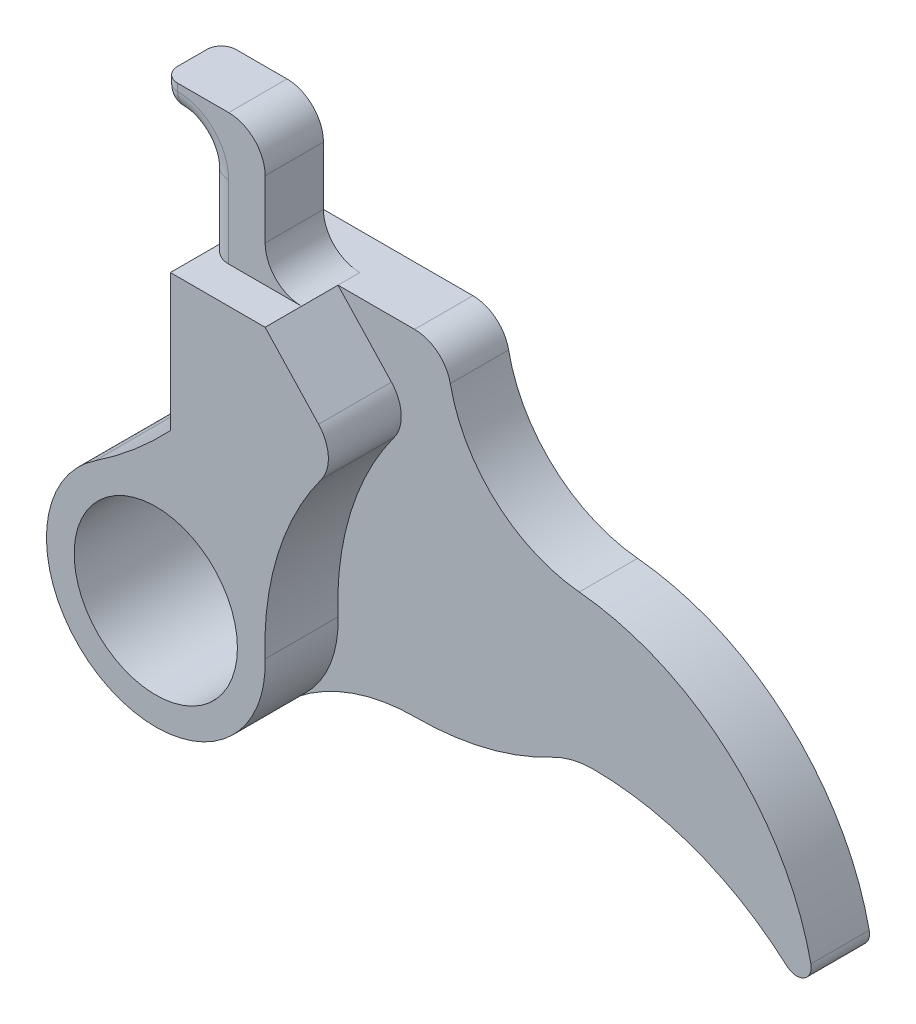
SolidWorks part; units mm, degrees
ref_plane "Спереди" through (0, 0, 0) normal (0, 0, 1) x (1, 0, 0)
ref_plane "Сверху" through (0, 0, 0) normal (0, 1, 0) x (1, 0, 0)
ref_plane "Справа" through (0, 0, 0) normal (1, 0, 0) x (0, 0, -1)
sketch "base" plane through (0, 0, 0) normal (0, 0, 1) x (1, 0, 0)
  line L0 (0, -25) -> (-25, -20) construction
  line L1 (0, 0) -> (9.5671, -23.097) construction
  line L2 (0, 0) -> (-9.5671, -23.097) construction
  line L3 (0, 0) -> (0, -25) construction
  line L4 (0, 0) -> (-2.4504, -24.8796) construction
  line L6 (0, 0) -> (-4.8773, -24.5196) construction
  line L7 (0, -25) -> (25, -20) construction
  line L11 (0, 0) -> (-7.2571, -23.9235) construction
  line L14 (0, 0) -> (7.2571, -23.9235) construction
  line L16 (0, 0) -> (4.8773, -24.5196) construction
  line L18 (0, 0) -> (2.4504, -24.8796) construction
  line L19 (-9.5671, -23.097) -> (9.5671, -23.097) construction
  arc A0 (-7.6537, -18.4776) -> (7.6537, -18.4776) centre (0, 0) ccw construction
  circle A1 centre (0, -25) radius 5 construction
  arc A6 (-9.5671, -23.097) -> (9.5671, -23.097) centre (0, 0) ccw construction
  point P12 (0, -20)
  dimension "D5" = 45
  dimension "D12" = 20
  dimension "ArmA" = 25
  dimension "ArmB" = 25.4951
  dimension "R" = 5
  dimension "base_offset" = 25
  dimension "stick_leverage" = 25
sketch "base-curve" plane through (0, 0, 0) normal (0, 0, 1) x (1, 0, 0)
  line L0 (0, -20) -> (0, -25) construction
  line L1 (0, 0) -> (-2.4504, -24.8796) construction
  line L2 (0, 0) -> (2.4504, -24.8796) construction
  line L5 (-25, -20) -> (0, -20) construction
  line L6 (0, -20) -> (25, -20) construction
  line L7 (10, -20) -> (10, 0) construction
  line L8 (-10, -20) -> (-10, 0) construction
  line L9 (-10, 0) -> (10, 0) construction
  line L10 (-25, -20) -> (-10, 0) construction
  line L11 (10, 0) -> (25, -20) construction
  line L13 (0, 0) -> (-4.8773, -24.5196) construction
  line L14 (0, 0) -> (4.8773, -24.5196) construction
  line L15 (0, 0) -> (-7.2571, -23.9235) construction
  line L16 (0, 0) -> (-9.5671, -23.097) construction
  line L17 (-2.2605, -20.5401) -> (-4.3096, -21.5787)
  line L18 (-4.3096, -21.5787) -> (-6.5058, -22.3844)
  line L19 (-6.5058, -22.3844) -> (-9.5586, -23.0612)
  line L20 (-9.5586, -23.0612) -> (-12.1501, -23.2901)
  line L21 (-2.5877, -26.2729) -> (-4.3096, -21.5787) construction
  line L22 (-8.4763, -27.9427) -> (-9.5586, -23.0612) construction
  line L23 (-5.4235, -27.2658) -> (-6.5058, -22.3844) construction
  line L24 (-11.7101, -28.2707) -> (-12.1501, -23.2901) construction
  line L25 (-22.6762, -27.1309) -> (-1.5492, -20.2461) construction
  line L26 (0, 0) -> (7.2571, -23.9235) construction
  line L27 (0, 0) -> (9.5671, -23.097) construction
  circle A0 centre (0, -25) radius 5 construction
  circle A1 centre (2.6465, -26.87) radius 5 construction
  circle A2 centre (-2.5877, -26.2729) radius 5 construction
  circle A4 centre (-5.4235, -27.2658) radius 5 construction
  circle A5 centre (-8.4763, -27.9427) radius 5 construction
  circle A6 centre (-25, -20) radius 7.5 construction
  circle A7 centre (-11.7101, -28.2707) radius 5 construction
  circle A8 centre (5.6576, -28.4428) radius 5 construction
  circle A9 centre (8.9988, -29.6652) radius 5 construction
  circle A10 centre (12.6286, -30.488) radius 5 construction
  point P3 (2.4504, -24.8796)
  point P11 (2.6465, -26.87)
  point P24 (-2.4504, -24.8796)
  point P25 (4.8773, -24.5196)
  point P27 (-4.8773, -24.5196)
  point P33 (-7.2571, -23.9235)
  point P36 (-9.5671, -23.097)
  point P39 (-2.5877, -26.2729)
  point P40 (5.6576, -28.4428)
  point P41 (-5.4235, -27.2658)
  point P42 (-8.4763, -27.9427)
  point P43 (-11.7101, -28.2707)
  point P64 (7.2571, -23.9235)
  point P65 (8.9988, -29.6652)
  point P68 (9.5671, -23.097)
  point P69 (12.6286, -30.488)
  dimension "D13" = 15
  dimension "spring" = 20
  dimension "b_long" = 53.13
  dimension "b_short" = 53.13
  dimension "D3" = 1.4
  dimension "D4" = 2.8
  dimension "D5" = 4.2
  dimension "D6" = 5.6
  dimension "D2" = 2
  dimension "D7" = 4
  dimension "D8" = 6
  dimension "D9" = 8
sketch "Эскиз2" plane through (0, 0, 0) normal (0, 0, 1) x (1, 0, 0)
  line L0 (-11.7101, -28.2707) -> (-12.1749, -23.0095) construction
  line L1 (-10, 0) -> (-18, 0) construction
  line L3 (-2.2605, -20.5401) -> (-4.3096, -21.5787) construction
  line L4 (0, -25) -> (0, 0) construction
  line L10 (-4.3096, -21.5787) -> (-6.5058, -22.3844) construction
  line L11 (-22.6602, -27.1257) -> (-1.8719, -20.2995) construction
  line L12 (-6.5058, -22.3844) -> (-9.5586, -23.0612) construction
  line L13 (-9.5586, -23.0612) -> (-12.1501, -23.2901) construction
  line L14 (-2.2605, -20.5401) -> (-4.3096, -21.5787) construction
  line L15 (-4.3096, -21.5787) -> (-6.5058, -22.3844) construction
  line L16 (-6.5058, -22.3844) -> (-9.5586, -23.0612) construction
  line L17 (-9.5586, -23.0612) -> (-12.1501, -23.2901) construction
  line L18 (-24, 0) -> (-24, -10.4037)
  line L19 (0, -25) -> (0, -40) construction
  line L20 (0, -40) -> (15.3209, -27.1442) construction
  line L23 (-10, 0) -> (-10, 7)
  line L24 (-10, 7) -> (-24, 7)
  line L25 (-24, 0) -> (-24, 7)
  circle A0 centre (-25, -20) radius 7.5 construction
  arc A1 (-2.8021, -20.6945) -> (-12.1749, -23.0095) centre (-12.1425, -3.0096) cw
  arc A2 (-29.1682, -13.7649) -> (-20.3156, -25.8571) centre (-25, -20) ccw
  arc A3 (15.3209, -27.1442) -> (0, -20) centre (0, -40) ccw
  arc A5 (-29.1682, -13.7649) -> (-18, 0) centre (-45.8408, 11.1755) ccw
  arc A6 (-7.6537, -18.4776) -> (7.6537, -18.4776) centre (0, 0) ccw construction
  arc A7 (-9.5671, -23.097) -> (9.5671, -23.097) centre (0, 0) ccw construction
  arc A8 (-2.8021, -20.6945) -> (0, -20) centre (0, -26) cw
  arc A10 (15.3209, -27.1442) -> (-0.9516, -9.9546) centre (-2.6644, -27.8729) ccw
  arc A11 (-0.9516, -9.9546) -> (-10, 0) centre (0, 0) cw
  arc A13 (-16.899, -23.8901) -> (-9.55, -2.9661) centre (2.4797, -18.9437) cw construction
  arc A17 (-20.3156, -25.8571) -> (-12.1749, -23.0095) centre (-12.1959, -36.0095) cw
  point P48 (-2.5877, -26.2729)
  point P52 (-5.4235, -27.2658)
  point P54 (-8.4763, -27.9427)
  point P56 (-11.7101, -28.2707)
  dimension "D2" = 6
  dimension "D3" = 14
  dimension "D4" = 3
  dimension "D5" = 30
  dimension "D6" = 50
  dimension "D8" = 18
  dimension "80" = 20
  dimension "D9" = 20
  dimension "D10" = 20
  dimension "D11" = 7
  dimension "D14" = 13
  dimension "D7" = 10
  dimension "D1" = 8
extrude "Бобышка-Вытянуть1" add sketch "Эскиз2" along normal blind 9 contours A2 A17 A1 A8 A3 A10 A11 L23 L24 L25 L18 A5 region at (-13.0986, -12.5264, 0)
sketch "Эскиз6" plane through (0, 0, 9) normal (0, 0, 1) x (1, 0, 0)
  arc A0 (-9.55, -2.9661) -> (-16.899, -23.8901) centre (2.4797, -18.9437) ccw construction
  arc A1 (-9.55, -2.9661) -> (-16.899, -23.8901) centre (2.4797, -18.9437) ccw
  arc A5 (-10, 0) -> (-0.9516, -9.9546) centre (0, 0) ccw construction
  arc A6 (15.3209, -27.1442) -> (-0.9516, -9.9546) centre (-2.6644, -27.8729) ccw
  arc A7 (-9.55, -2.9661) -> (-0.9516, -9.9546) centre (0, 0) ccw
  arc A8 (15.3209, -27.1442) -> (0, -20) centre (0, -40) ccw
  arc A11 (-12.1749, -23.0095) -> (-16.899, -23.8901) centre (-12.1959, -36.0095) ccw
  arc A12 (-12.1749, -23.0095) -> (-2.8021, -20.6945) centre (-12.1425, -3.0096) ccw
  arc A13 (0, -20) -> (-2.8021, -20.6945) centre (0, -26) ccw
extrude "Вырез-Вытянуть1" cut sketch "Эскиз6" against normal blind 5
sketch "Эскиз12" plane through (-24, 0, 0) normal (-1, 0, 0) x (0, 0, 1)
  line L1 (0, 7) -> (2.5, 7)
  line L2 (0, 7) -> (0, 0)
  line L3 (0, 0) -> (2.5, 0)
  line L4 (2.5, 7) -> (2.5, 0)
  line L5 (4.5, 0) -> (4.5, 7) construction
  line L6 (9, 7) -> (0, 7) construction
  line L7 (6.5, 7) -> (6.5, 0)
  line L8 (9, 0) -> (6.5, 0)
  line L9 (9, 7) -> (9, 0)
  line L10 (9, 7) -> (6.5, 7)
  point P4 (0, 0)
  point P15 (0, 0)
  point P16 (0, 0)
  dimension "D1" = 4
extrude "Вырез-Вытянуть3" cut sketch "Эскиз12" against normal through all
fillet "Скругление1" radius 1 1 edges at (15.3209, -27.1442, 2)
sketch "Эскиз10" plane through (0, 7, 0) normal (0, 1, 0) x (-1, 0, 0)
  line L0 (10, 6.5) -> (24, 6.5) construction
  line L1 (10, 2.5) -> (27, 2.5)
  line L2 (10, 2.5) -> (10, 6.5)
  line L3 (10, 6.5) -> (27, 6.5)
  line L4 (27, 2.5) -> (27, 6.5)
  line L5 (10, 6.5) -> (10, 2.5) construction
  line L6 (24, 6.5) -> (24, 2.5) construction
  dimension "D1" = 3
extrude "Бобышка-Вытянуть3" add sketch "Эскиз10" along normal blind 2
fillet "Скругление5" radius 5 1 edges at (-10, 9, 4.5)
fillet "Скругление10" radius 7.5 1 edges at (-16.899, -23.8901, 6.5)
fillet "Скругление14" radius 2 1 edges
fillet "Скругление15" radius 1.5 6 edges at (-24.5858, 6.4142, 2.5) (-24.5858, 6.4142, 6.5)
fillet "Скругление17" radius 1 5 edges at (-27, 8.75, 2.5) (-27, 7.4393, 2.9393) (-27, 7, 4.5) (-27, 8.75, 6.5) (-27, 7.4393, 6.0607)
fillet "Скругление18" radius 2 1 edges at (-9.55, -2.9661, 6.5)
sketch "Эскиз11" plane through (0, 0, 9) normal (0, 0, 1) x (1, 0, 0)
  circle A0 centre (-25, -20) radius 5.5 construction
  circle A2 centre (-25, -20) radius 5.6
  point P7 (0, 0)
  dimension "D1" = 11
  dimension "tolerance" = 0.1
extrude "Вырез-Вытянуть2" cut sketch "Эскиз11" against normal through all
sketch "Sketch1" plane through (0, 0, 6.5) normal (0, 0, 1) x (1, 0, 0)
  line L0 (-20, 9) -> (-20, 0)
  line L1 (-26, 9) -> (-15, 9) construction
  line L2 (-10, 0) -> (-22.5, 0) construction
  line L3 (-20, 0) -> (-10, 0)
  line L4 (-10, 0) -> (-10, 9)
  line L5 (-10, 9) -> (-20, 9)
  line L6 (-24, 0) -> (-24, 5) construction
  dimension "D1" = 4
extrude "Cut-Extrude1" cut sketch "Sketch1" against normal blind 10
fillet "Fillet1" radius 2.5 2 edges at (-20, 0, 4.5) (-20, 9, 4.5)
sketch "Sketch3" plane through (0, 0, 4) normal (0, 0, 1) x (1, 0, 0)
  line L0 (-17.5, 0) -> (-12.3481, -5.5223)
  line L1 (-17.5, 0) -> (-10, 0)
  line L2 (-10, 0) -> (-8.9328, -2.5543)
  line L3 (-8.9328, -2.5543) -> (-12.3481, -5.5223)
  arc A0 (-10.498, -3.726) -> (-17.5055, -19.7119) centre (2.4797, -18.9437) ccw construction
extrude "Cut-Extrude2" cut sketch "Sketch3" along normal blind 10
fillet "Fillet2" radius 2.5 2 edges at (-12.3481, -5.5223, 6.5) (-10, 0, 2)
equation "\"rad\"= 0.0174533"
equation "\"radius_offset\"= 10"
equation "\"spring_power\"= 200'g"
equation "\"D4@base-curve\"=\"D3@base-curve\"*2"
equation "\"D5@base-curve\"=\"D3@base-curve\"*3"
equation "\"D6@base-curve\"=\"D3@base-curve\"*4"
equation "\"D7@base-curve\"=\"D2@base-curve\"*2"
equation "\"D8@base-curve\"=\"D2@base-curve\"*3"
equation "\"D9@base-curve\"=\"D2@base-curve\"*4"
